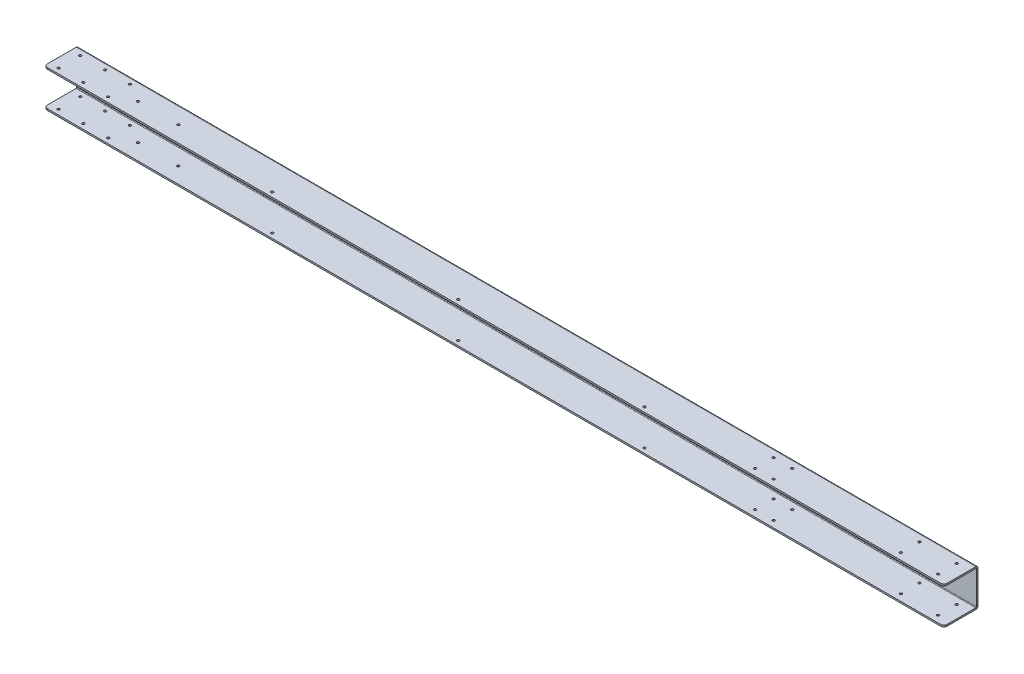
SolidWorks part; units mm, degrees
note: The reader was unsure of these and kept them because the rebuilt part matched: flange length of "Edge-Flange1".
material "5052-H32"
ref_plane "Front Plane" through (0, 0, 0) normal (0, 0, 1) x (1, 0, 0)
ref_plane "Top Plane" through (0, 0, 0) normal (0, 1, 0) x (1, 0, 0)
ref_plane "Right Plane" through (0, 0, 0) normal (1, 0, 0) x (0, 0, -1)
sketch "Sketch2" plane through (0, 0, 0) normal (0, 0, 1) x (1, 0, 0)
  line L1 (-920.75, 34.8361) -> (920.75, 34.8361)
  line L2 (-920.75, 34.8361) -> (-920.75, -34.8361)
  line L3 (-920.75, -34.8361) -> (920.75, -34.8361)
  line L4 (920.75, 34.8361) -> (920.75, -34.8361)
  line L5 (-920.75, 34.8361) -> (920.75, -34.8361) construction
  line L6 (-920.75, -34.8361) -> (920.75, 34.8361) construction
  point P0 (0, 0)
  dimension "D1" = 1841.5
  dimension "D2" = 69.6722
base flange "Base-Flange1" sketch "Sketch2" thickness 3.2639 reverse thickness direction no parameters "D1"=1.27
edge flange "Edge-Flange1" sketch "Sketch11" flange profiles "Sketch11", "Sketch12" flange angle 90 flange length 69.85 flange position material outside bend radius 1.27 thickness 3.2639 relief rectangular parameters "D6"=10, "D8"=0.254
sketch "Sketch11" plane through (0, 34.8361, 0) normal (0, 1, 0) x (-1, 0, 0)
  line L0 (-920.75, 0) -> (920.75, 0) construction
  line L1 (-920.75, 0) -> (920.75, 0)
  line L2 (-920.75, 0) -> (-920.75, 66.5861)
  line L3 (-920.75, 66.5861) -> (920.75, 66.5861)
  line L4 (920.75, 66.5861) -> (920.75, 0)
sketch "Sketch12" plane through (0, -34.8361, 0) normal (0, -1, 0) x (1, 0, 0)
  line L0 (-920.75, 0) -> (920.75, 0) construction
  line L1 (-920.75, 0) -> (920.75, 0)
  line L2 (-920.75, 0) -> (-920.75, 66.5861)
  line L3 (-920.75, 66.5861) -> (920.75, 66.5861)
  line L4 (920.75, 66.5861) -> (920.75, 0)
bend "EdgeBend1" bend radius 1.27 bend angle 90 parameters "D5"=1
bend "EdgeBend2" bend radius 1.27 bend angle 90 parameters "D5"=2
edge flange "Edge-Flange2" [suppressed] sketch "Sketch17" flange profiles "Sketch17", "Sketch18" flange angle 90 flange position material inside bend radius 1.27 thickness 3.2639
sketch "Sketch17" plane through (0, 34.8361, 66.5861) normal (0, 0, -1) x (1, 0, 0)
  line L2 (-920.75, 0) -> (-920.75, 11.9761)
  line L3 (-920.75, 11.9761) -> (920.75, 11.9761)
  line L4 (920.75, 11.9761) -> (920.75, 0)
  line L5 (920.75, 0) -> (-920.75, 0) construction
  line L6 (920.75, 0) -> (-920.75, 0)
sketch "Sketch18" plane through (0, -34.8361, 66.5861) normal (0, 0, -1) x (-1, 0, 0)
  line L0 (920.75, 0) -> (-920.75, 0) construction
  line L1 (920.75, 0) -> (-920.75, 0)
  line L2 (920.75, 0) -> (920.75, 11.9761)
  line L3 (920.75, 11.9761) -> (-920.75, 11.9761)
  line L4 (-920.75, 11.9761) -> (-920.75, 0)
bend "EdgeBend3" bend radius 1.27 bend angle 90 parameters "D5"=3
bend "EdgeBend4" bend radius 1.27 bend angle 90 parameters "D5"=4, "D6"=10, "D7"=15.24
sketch "Sketch26" plane through (0, 38.1, 0) normal (0, 1, 0) x (1, 0, 0)
  line L0 (-920.75, -1.27) -> (-920.75, -66.5861) construction
  line L1 (-901.7, -11.7031) -> (-800.1, -11.7031)
  line L2 (-901.7, -11.7031) -> (-901.7, -56.1531)
  line L3 (-901.7, -56.1531) -> (-800.1, -56.1531)
  line L4 (-800.1, -11.7031) -> (-800.1, -56.1531)
  point P6 (-850.9, -56.1531)
  point P7 (-920.75, -33.9281)
  point P8 (-901.7, -33.9281)
  point P10 (-850.9, -11.7031)
  dimension "D1" = 19.05
  dimension "D2" = 44.45
  dimension "D3" = 50.8
hole_wizard "#10 (0.1935) Diameter Hole1" positions "Sketch20" profile "Sketch21" hole size "#10" standard "ANSI Inch" end condition through all
sketch "Sketch20" plane through (0, 38.1, 34.8361) normal (0, -1, 0) x (-1, 0, 0)
  point P21 (800.1, 23.133)
  point P23 (800.1, -21.317)
  point P25 (850.9, -21.317)
  point P27 (850.9, 23.133)
  point P29 (901.7, -21.317)
  point P31 (901.7, 23.133)
sketch "Sketch21" plane through (-800.1, 38.1, 11.703) normal (1, 0, 0) x (0, 0, 1)
  line L0 (0, 0) -> (0, 76.2)
  line L1 (0, 76.2) -> (2.4574, 76.2)
  line L2 (2.4574, 76.2) -> (2.4574, 0)
  line L5 (2.4574, 0) -> (0, 0)
  line L11 (0, -6.35) -> (0, 107.95) construction
  dimension "Thru Hole Dia." = 4.9149
  dimension "Thru Hole Depth" = 76.2
sketch "Sketch22" [suppressed] plane through (0, 0, 82.3722) normal (0, 0, 1) x (1, 0, 0)
  line L0 (-920.75, 38.1) -> (920.75, 38.1) construction
  line L1 (-920.75, 22.86) -> (-920.75, 33.5661) construction
  line L2 (920.75, -38.1) -> (-920.75, -38.1) construction
  point P0 (-844.55, 28.575)
  point P5 (-844.55, -28.575)
  dimension "D1" = 9.525
  dimension "D2" = 76.2
  dimension "D3" = 9.525
hole_wizard "#10 (0.1935) Diameter Hole2" [suppressed] positions "Sketch23" profile "Sketch24" hole size "#10" standard "ANSI Inch"
sketch "Sketch23" [suppressed] plane through (0, 0, 82.3722) normal (0, 0, 1) x (1, 0, 0)
  point P0 (-844.55, 28.575)
  point P3 (-844.55, -28.575)
sketch "Sketch24" plane through (-844.55, 28.575, 82.3722) normal (1, 0, 0) x (0, -1, 0)
  line L0 (0, 0) -> (0, 85.6361)
  line L1 (0, 85.6361) -> (2.4574, 85.6361)
  line L2 (2.4574, 85.6361) -> (2.4574, 0)
  line L5 (2.4574, 0) -> (0, 0)
  line L11 (0, -6.35) -> (0, 107.95) construction
  dimension "Thru Hole Dia." = 4.9149
  dimension "Thru Hole Depth" = 85.6361
pattern_linear "LPattern1" [suppressed] count 11 spacing 168.91
sketch "Sketch27" plane through (0, 38.1, 0) normal (0, 1, 0) x (1, 0, 0)
  line L0 (819.15, -14.8781) -> (819.15, -52.9781) construction
  line L3 (895.35, -33.9281) -> (920.75, -33.9281) construction
  line L4 (895.35, -14.8781) -> (895.35, -52.9781) construction
  line L6 (920.75, -66.5861) -> (920.75, -1.27) construction
  dimension "D1" = 38.1
  dimension "D2" = 25.4
  dimension "D4" = 76.2
hole_wizard "#10 (0.1935) Diameter Hole3" positions "Sketch28" profile "Sketch29" hole size "#10" standard "ANSI Inch" end condition through all
sketch "Sketch28" plane through (0, 38.1, 0) normal (0, 1, 0) x (1, 0, 0)
  point P0 (819.15, -14.8781)
  point P3 (819.15, -52.9781)
  point P6 (895.35, -14.8781)
  point P9 (895.35, -52.9781)
sketch "Sketch29" plane through (819.15, 38.1, 14.878) normal (1, 0, 0) x (0, 0, 1)
  line L0 (0, 0) -> (0, 76.2)
  line L1 (0, 76.2) -> (2.4574, 76.2)
  line L2 (2.4574, 76.2) -> (2.4574, 0)
  line L5 (2.4574, 0) -> (0, 0)
  line L11 (0, -6.35) -> (0, 107.95) construction
  dimension "Thru Hole Dia." = 4.9149
  dimension "Thru Hole Depth" = 76.2
sketch "Sketch31" plane through (0, 38.1, 0) normal (0, 1, 0) x (1, 0, 0)
  line L0 (920.75, -66.5861) -> (920.75, -1.27) construction
  line L1 (520.7, -14.8781) -> (558.8, -14.8781)
  line L2 (520.7, -14.8781) -> (520.7, -52.9781)
  line L3 (520.7, -52.9781) -> (558.8, -52.9781)
  line L4 (558.8, -14.8781) -> (558.8, -52.9781)
  point P4 (558.8, -33.9281)
  point P7 (920.75, -33.9281)
  point P8 (539.75, -14.8781)
  dimension "D1" = 38.1
  dimension "D2" = 38.1
  dimension "D3" = 381
hole_wizard "#10 (0.1935) Diameter Hole4" positions "Sketch32" profile "Sketch33" hole size "#10" standard "ANSI Inch" end condition through all
sketch "Sketch32" plane through (0, 38.1, 0) normal (0, 1, 0) x (1, 0, 0)
  point P0 (520.7, -14.8781)
  point P3 (558.8, -14.8781)
  point P6 (558.8, -52.9781)
  point P9 (520.7, -52.9781)
sketch "Sketch33" plane through (520.7, 38.1, 14.878) normal (1, 0, 0) x (0, 0, 1)
  line L0 (0, 0) -> (0, 76.2)
  line L1 (0, 76.2) -> (2.4574, 76.2)
  line L2 (2.4574, 76.2) -> (2.4574, 0)
  line L5 (2.4574, 0) -> (0, 0)
  line L11 (0, -6.35) -> (0, 107.95) construction
  dimension "Thru Hole Dia." = 4.9149
  dimension "Thru Hole Depth" = 76.2
sketch "Sketch35" [suppressed] plane through (0, 38.1, 0) normal (0, 1, 0) x (1, 0, 0)
  line L0 (49980.8586, -68.2181) -> (-49980.8586, -68.2181) construction
  line L1 (920.75, -66.5861) -> (-920.75, -66.5861) construction
  line L2 (-787.4, -9.4361) -> (-787.4, -53.8861) construction
  circle A0 centre (-800.1, -53.8861) radius 2.4574 construction
  point P2 (0, -68.2181)
  point P12 (-762, -31.6611)
  point P13 (-679.45, -31.6611)
  point P14 (-787.4, -31.6611)
  dimension "D2" = 12.7
  dimension "D1" = 1.632
  dimension "D3" = 25.4
  dimension "D4" = 82.55
hole_wizard "#10 (0.1935) Diameter Hole5" [suppressed] positions "Sketch36" profile "Sketch37" hole size "#10" standard "ANSI Inch"
sketch "Sketch36" [suppressed] plane through (0, 38.1, 0) normal (0, 1, 0) x (1, 0, 0)
  point P0 (-762, -39.5542)
  point P3 (-679.45, -39.5542)
sketch "Sketch37" [suppressed] plane through (-762, 38.1, 39.5541) normal (1, 0, 0) x (0, 0, 1)
  line L0 (0, 0) -> (0, 76.2)
  line L1 (0, 76.2) -> (2.4574, 76.2)
  line L2 (2.4574, 76.2) -> (2.4574, 0)
  line L5 (2.4574, 0) -> (0, 0)
  line L11 (0, -6.35) -> (0, 107.95) construction
  dimension "Thru Hole Dia." = 4.9149
  dimension "Thru Hole Depth" = 76.2
fillet "Fillet1" [suppressed] radius 6.35
sketch "Sketch41" plane through (0, 38.1, 0) normal (0, 1, 0) x (1, 0, 0)
  line L0 (-800.1, -56.1531) -> (-800.1, -11.7031) construction
  point P4 (-761.3205, -33.9281)
  point P5 (-678.7705, -33.9281)
  point P6 (-800.1, -33.9281)
  dimension "D1" = 38.7794
  dimension "D2" = 82.55
hole_wizard "#10 (0.2) Diameter Hole1" positions "Sketch42" profile "Sketch43" hole size "#10" standard "ANSI Inch" end condition through all
sketch "Sketch42" plane through (0, 38.1, 0) normal (0, 1, 0) x (1, 0, 0)
  point P0 (-761.3205, -33.9281)
  point P3 (-678.7705, -33.9281)
sketch "Sketch43" plane through (-761.3205, 38.1, 33.928) normal (1, 0, 0) x (0, 0, 1)
  line L0 (0, 0) -> (0, 76.2)
  line L1 (0, 76.2) -> (2.54, 76.2)
  line L2 (2.54, 76.2) -> (2.54, 0)
  line L5 (2.54, 0) -> (0, 0)
  line L11 (0, -6.35) -> (0, 107.95) construction
  dimension "Thru Hole Dia." = 5.08
  dimension "Thru Hole Depth" = 76.2
sketch "Sketch38" plane through (0, -38.1, 0) normal (0, -1, 0) x (1, 0, 0)
  line L0 (-920.75, 66.5861) -> (-920.75, 1.27) construction
  line L1 (920.75, 66.5861) -> (-920.75, 66.5861) construction
  point P0 (-463.55, 57.0611)
  dimension "D1" = 457.2
  dimension "D2" = 9.525
hole_wizard "#10 (0.1935) Diameter Hole6" positions "Sketch39" profile "Sketch40" hole size "#10" standard "ANSI Inch" end condition through all
sketch "Sketch39" plane through (0, -38.1, 0) normal (0, -1, 0) x (-1, 0, 0)
  point P0 (463.55, -57.0611)
sketch "Sketch40" plane through (-463.55, -38.1, 57.0611) normal (1, 0, 0) x (0, 0, -1)
  line L0 (0, 0) -> (0, 76.2)
  line L1 (0, 76.2) -> (2.4574, 76.2)
  line L2 (2.4574, 76.2) -> (2.4574, 0)
  line L5 (2.4574, 0) -> (0, 0)
  line L11 (0, -6.35) -> (0, 107.95) construction
  dimension "Thru Hole Dia." = 4.9149
  dimension "Thru Hole Depth" = 76.2
pattern_linear "LPattern2" count 3 spacing 381 along (1, 0, 0) of "#10 (0.1935) Diameter Hole6"
fillet "Fillet2" radius 6.35 4 edges at (920.75, -36.4681, 66.5861) (920.75, 36.4681, 66.5861) (-920.75, -36.4681, 66.5861) (-920.75, 36.4681, 66.5861)
sketch "Bend-Lines1" [suppressed] plane through (0, 0, 0) normal (0, 1, 0) x (1, 0, 0)
sketch "Bounding-Box1" [suppressed] plane through (0, 0, 0) normal (0, 1, 0) x (1, 0, 0)
sheet metal parameters "Sheet-Metal1" thickness 3.2639 parameters "D1"=1.27
flat pattern "Flat-Pattern1" [suppressed]
sketch "Bend-Lines2" plane through (0, 0, 0) normal (0, 1, 0) x (1, 0, 0)
sketch3d "Bounding-Box2" [suppressed]
  line L0 (908.05, -44.45, 0) -> (-908.05, -44.45, 0) construction
  line L1 (908.05, 44.45, 0) -> (-908.05, 44.45, 0) construction
  line L2 (908.05, -44.45, 0) -> (908.05, 44.45, 0) construction
  line L3 (-908.05, -44.45, 0) -> (-908.05, 44.45, 0) construction
sheet metal parameters "Sheet-Metal2" thickness 3.2639 parameters "D1"=1.27
flat pattern "Flat-Pattern1" [suppressed]
sketch "Bend-Lines2" plane through (0, 0, 0) normal (0, 0, 1) x (1, 0, 0)
  line L0 (-908.05, -42.1953) -> (908.05, -42.1953) construction
  line L1 (908.05, 42.1953) -> (-908.05, 42.1953) construction
  line L2 (-908.05, -42.1953) -> (908.05, -42.1953) construction
  line L3 (908.05, 42.1953) -> (-908.05, 42.1953) construction
sketch3d "Bounding-Box2" [suppressed]
  line L0 (-908.05, -103.4406, 0) -> (908.05, -103.4406, 0) construction
  line L1 (-908.05, 103.4406, 0) -> (908.05, 103.4406, 0) construction
  line L2 (-908.05, -103.4406, 0) -> (-908.05, 103.4406, 0) construction
  line L3 (908.05, -103.4406, 0) -> (908.05, 103.4406, 0) construction
bend of the flat pattern "Flatten-<EdgeBend1>1"
bend of the flat pattern "Flatten-<EdgeBend2>1"
sheet metal parameters "Sheet-Metal3" thickness 3.2639 parameters "D1"=1.27
flat pattern "Flat-Pattern1" [suppressed]
sketch "Bend-Lines2" plane through (0, 0, 0) normal (0, 0, 1) x (1, 0, 0)
  line L0 (-920.75, -35.8453) -> (920.75, -35.8453) construction
  line L1 (920.75, 35.8453) -> (-920.75, 35.8453) construction
  line L2 (-920.75, -35.8453) -> (920.75, -35.8453) construction
  line L3 (920.75, 35.8453) -> (-920.75, 35.8453) construction
  line L4 (-920.75, -116.972) -> (920.75, -116.972) construction
  line L5 (920.75, 116.972) -> (-920.75, 116.972) construction
  line L6 (-920.75, -116.972) -> (920.75, -116.972) construction
  line L7 (920.75, 116.972) -> (-920.75, 116.972) construction
sketch3d "Bounding-Box2" [suppressed]
  line L0 (-920.75, -140.1172, 0) -> (920.75, -140.1172, 0) construction
  line L1 (-920.75, 140.1172, 0) -> (920.75, 140.1172, 0) construction
  line L2 (-920.75, -140.1172, 0) -> (-920.75, 140.1172, 0) construction
  line L3 (920.75, -140.1172, 0) -> (920.75, 140.1172, 0) construction
bend of the flat pattern "Flatten-<EdgeBend3>1"
bend of the flat pattern "Flatten-<EdgeBend4>1"
sketch "Sketch22-4" [suppressed] plane through (0, 152.8172, -3.2639) normal (0, 0, -1) x (1, 0, 0)
  line L0 (-920.75, 38.1) -> (920.75, 38.1)
  line L1 (-920.75, 12.7) -> (-920.75, 292.9345)
  line L2 (920.75, -38.1) -> (-920.75, -38.1)
  point P0 (-768.35, 22.225)
  point P5 (-768.35, -22.225)
  dimension "D1" = 15.875
  dimension "D2" = 152.4
  dimension "D3" = 15.875
bend of the flat pattern "Flatten-<EdgeBend1>1"
bend of the flat pattern "Flatten-<EdgeBend2>1"
sheet metal parameters "Sheet-Metal4" thickness 3.2639 parameters "D1"=1.27
flat pattern "Flat-Pattern1" [suppressed]
sketch "Bend-Lines2" plane through (0, 0, 0) normal (0, 0, 1) x (1, 0, 0)
  line L0 (-920.75, -35.8453) -> (920.75, -35.8453) construction
  line L1 (920.75, 35.8453) -> (-920.75, 35.8453) construction
  line L2 (-920.75, -35.8453) -> (920.75, -35.8453) construction
  line L3 (920.75, 35.8453) -> (-920.75, 35.8453) construction
  line L4 (-920.75, -116.972) -> (920.75, -116.972) construction
  line L5 (920.75, 116.972) -> (-920.75, 116.972) construction
  line L6 (-920.75, -116.972) -> (920.75, -116.972) construction
  line L7 (920.75, 116.972) -> (-920.75, 116.972) construction
sketch3d "Bounding-Box2" [suppressed]
  line L0 (-920.75, -140.1172, 0) -> (920.75, -140.1172, 0) construction
  line L1 (-920.75, 140.1172, 0) -> (920.75, 140.1172, 0) construction
  line L2 (-920.75, -140.1172, 0) -> (-920.75, 140.1172, 0) construction
  line L3 (920.75, -140.1172, 0) -> (920.75, 140.1172, 0) construction
sketch "Sketch22-3" [suppressed] plane through (0, 152.8172, -3.2639) normal (0, 0, -1) x (1, 0, 0)
  line L0 (-920.75, 38.1) -> (920.75, 38.1)
  line L1 (-920.75, 12.7) -> (-920.75, 292.9345)
  line L2 (920.75, -38.1) -> (-920.75, -38.1)
  point P0 (-768.35, 22.225)
  point P5 (-768.35, -22.225)
  dimension "D1" = 15.875
  dimension "D2" = 152.4
  dimension "D3" = 15.875
sketch "Sketch26-1" [suppressed] plane through (0, 36.8545, -3.2639) normal (0, 0, -1) x (1, 0, 0)
  line L0 (-920.75, 176.9717) -> (-920.75, -103.2628)
  line L1 (-901.7, -14.1542) -> (-800.1, -14.1542)
  line L2 (-901.7, -14.1542) -> (-901.7, -64.9542)
  line L3 (-901.7, -64.9542) -> (-800.1, -64.9542)
  line L4 (-800.1, -14.1542) -> (-800.1, -64.9542)
  point P6 (-850.9, -64.9542)
  point P10 (-850.9, -14.1542)
  dimension "D1" = 19.05
  dimension "D2" = 50.8
  dimension "D3" = 50.8
bend of the flat pattern "Flatten-<EdgeBend1>1"
bend of the flat pattern "Flatten-<EdgeBend2>1"
sheet metal parameters "Sheet-Metal6" thickness 3.2639 parameters "D1"=1.27
flat pattern "Flat-Pattern1" [suppressed]
sketch "Bend-Lines2" plane through (0, 0, 0) normal (0, 0, 1) x (1, 0, 0)
  line L0 (-923.925, -42.1953) -> (923.925, -42.1953) construction
  line L1 (923.925, 42.1953) -> (-923.925, 42.1953) construction
  line L2 (-923.925, -42.1953) -> (923.925, -42.1953) construction
  line L3 (923.925, 42.1953) -> (-923.925, 42.1953) construction
  line L4 (-923.925, -110.622) -> (923.925, -110.622) construction
  line L5 (923.925, 110.622) -> (-923.925, 110.622) construction
  line L6 (-923.925, -110.622) -> (923.925, -110.622) construction
  line L7 (923.925, 110.622) -> (-923.925, 110.622) construction
sketch3d "Bounding-Box2" [suppressed]
  line L0 (-923.925, -133.7672, 0) -> (923.925, -133.7672, 0) construction
  line L1 (-923.925, 133.7672, 0) -> (923.925, 133.7672, 0) construction
  line L2 (-923.925, -133.7672, 0) -> (-923.925, 133.7672, 0) construction
  line L3 (923.925, -133.7672, 0) -> (923.925, 133.7672, 0) construction
bend of the flat pattern "Flatten-<EdgeBend3>1"
bend of the flat pattern "Flatten-<EdgeBend4>1"
sketch "Sketch22-1" [suppressed] plane through (0, 152.8172, -3.2639) normal (0, 0, -1) x (1, 0, 0)
  line L0 (-923.925, 44.45) -> (923.925, 44.45)
  line L1 (-923.925, 19.05) -> (-923.925, 286.5845)
  line L2 (923.925, -44.45) -> (-923.925, -44.45)
  point P0 (-796.925, 28.575)
  point P5 (-796.925, -28.575)
  dimension "D1" = 15.875
  dimension "D2" = 127
  dimension "D3" = 15.875
sheet metal parameters "Sheet-Metal7" thickness 3.2639 parameters "D1"=1.27
flat pattern "Flat-Pattern1" [suppressed]
sketch "Bend-Lines2" plane through (0, 0, 0) normal (0, 0, 1) x (1, 0, 0)
  line L0 (-920.75, -35.8453) -> (920.75, -35.8453) construction
  line L1 (920.75, 35.8453) -> (-920.75, 35.8453) construction
  line L2 (-920.75, -35.8453) -> (920.75, -35.8453) construction
  line L3 (920.75, 35.8453) -> (-920.75, 35.8453) construction
  line L4 (-920.75, -116.972) -> (920.75, -116.972) construction
  line L5 (920.75, 116.972) -> (-920.75, 116.972) construction
  line L6 (-920.75, -116.972) -> (920.75, -116.972) construction
  line L7 (920.75, 116.972) -> (-920.75, 116.972) construction
sketch3d "Bounding-Box2" [suppressed]
  line L0 (-920.75, -140.1172, 0) -> (920.75, -140.1172, 0) construction
  line L1 (-920.75, 140.1172, 0) -> (920.75, 140.1172, 0) construction
  line L2 (-920.75, -140.1172, 0) -> (-920.75, 140.1172, 0) construction
  line L3 (920.75, -140.1172, 0) -> (920.75, 140.1172, 0) construction
bend of the flat pattern "Flatten-<EdgeBend3>1"
bend of the flat pattern "Flatten-<EdgeBend4>1"
sketch "Sketch22-1" [suppressed] plane through (0, 152.8172, -3.2639) normal (0, 0, -1) x (1, 0, 0)
  line L0 (-920.75, 38.1) -> (920.75, 38.1)
  line L1 (-920.75, 12.7) -> (-920.75, 292.9345)
  line L2 (920.75, -38.1) -> (-920.75, -38.1)
  point P0 (-844.55, 22.225)
  point P5 (-844.55, -22.225)
  dimension "D1" = 15.875
  dimension "D2" = 76.2
  dimension "D3" = 15.875
sketch "Sketch26-2" [suppressed] plane through (0, 36.8545, -3.2639) normal (0, 0, -1) x (1, 0, 0)
  line L0 (-920.75, 176.9717) -> (-920.75, -103.2628)
  line L1 (-901.7, -14.1542) -> (-800.1, -14.1542)
  line L2 (-901.7, -14.1542) -> (-901.7, -64.9542)
  line L3 (-901.7, -64.9542) -> (-800.1, -64.9542)
  line L4 (-800.1, -14.1542) -> (-800.1, -64.9542)
  point P6 (-850.9, -64.9542)
  point P10 (-850.9, -14.1542)
  dimension "D1" = 19.05
  dimension "D2" = 50.8
  dimension "D3" = 50.8
sheet metal parameters "Sheet-Metal8" thickness 3.2639 parameters "D1"=1.27
flat pattern "Flat-Pattern1" [suppressed]
sketch "Bend-Lines2" plane through (0, 0, 0) normal (0, 0, 1) x (1, 0, 0)
  line L0 (-920.75, -35.8453) -> (920.75, -35.8453) construction
  line L1 (920.75, 35.8453) -> (-920.75, 35.8453) construction
  line L2 (-920.75, -35.8453) -> (920.75, -35.8453) construction
  line L3 (920.75, 35.8453) -> (-920.75, 35.8453) construction
  line L4 (-920.75, -116.972) -> (920.75, -116.972) construction
  line L5 (920.75, 116.972) -> (-920.75, 116.972) construction
  line L6 (-920.75, -116.972) -> (920.75, -116.972) construction
  line L7 (920.75, 116.972) -> (-920.75, 116.972) construction
sketch3d "Bounding-Box2" [suppressed]
  line L0 (-920.75, -140.1172, 0) -> (920.75, -140.1172, 0) construction
  line L1 (-920.75, 140.1172, 0) -> (920.75, 140.1172, 0) construction
  line L2 (-920.75, -140.1172, 0) -> (-920.75, 140.1172, 0) construction
  line L3 (920.75, -140.1172, 0) -> (920.75, 140.1172, 0) construction
sketch "Sketch22-1" [suppressed] plane through (0, 152.8172, -3.2639) normal (0, 0, -1) x (1, 0, 0)
  line L0 (-920.75, 38.1) -> (920.75, 38.1)
  line L1 (-920.75, 12.7) -> (-920.75, 292.9345)
  line L2 (920.75, -38.1) -> (-920.75, -38.1)
  point P0 (-844.55, 22.225)
  point P5 (-844.55, -22.225)
  dimension "D1" = 15.875
  dimension "D2" = 76.2
  dimension "D3" = 15.875
sketch "Sketch26-2" [suppressed] plane through (0, 36.8545, -3.2639) normal (0, 0, -1) x (1, 0, 0)
  line L0 (-920.75, 176.9717) -> (-920.75, -103.2628)
  line L1 (-901.7, -14.1542) -> (-800.1, -14.1542)
  line L2 (-901.7, -14.1542) -> (-901.7, -64.9542)
  line L3 (-901.7, -64.9542) -> (-800.1, -64.9542)
  line L4 (-800.1, -14.1542) -> (-800.1, -64.9542)
  point P6 (-850.9, -64.9542)
  point P10 (-850.9, -14.1542)
  dimension "D1" = 19.05
  dimension "D2" = 50.8
  dimension "D3" = 50.8
sketch "Sketch27-1" [suppressed] plane through (0, 36.8545, -3.2639) normal (0, 0, -1) x (1, 0, 0)
  line L0 (806.5132, -15.7861) -> (806.5132, -66.5861) construction
  line L1 (671.8955, -85.6361) -> (50671.8955, -85.6361) construction
  line L2 (-920.75, 3.2639) -> (920.75, 3.2639)
  line L3 (920.75, 3.2639) -> (920.75, -85.6361) construction
  line L4 (882.7132, -15.7861) -> (882.7132, -66.5861) construction
  dimension "D1" = 50.8
  dimension "D2" = 88.9
  dimension "D3" = 114.2368
  dimension "D4" = 76.2
bend of the flat pattern "Flatten-<EdgeBend1>1"
bend of the flat pattern "Flatten-<EdgeBend2>1"
sheet metal parameters "Sheet-Metal9" thickness 3.2639 parameters "D1"=1.27
flat pattern "Flat-Pattern1" [suppressed]
sketch "Bend-Lines2" plane through (0, 0, 0) normal (0, 0, 1) x (1, 0, 0)
  line L0 (-920.75, -35.9342) -> (920.75, -35.9342) construction
  line L1 (920.75, 35.9342) -> (-920.75, 35.9342) construction
  line L2 (-920.75, -35.9342) -> (920.75, -35.9342) construction
  line L3 (920.75, 35.9342) -> (-920.75, 35.9342) construction
sketch3d "Bounding-Box2" [suppressed]
  line L0 (-920.75, 103.5297, 0) -> (920.75, 103.5295, 0) construction
  line L1 (-920.75, -103.5293, 0) -> (920.75, -103.5295, 0) construction
  line L2 (-920.75, 103.5297, 0) -> (-920.75, -103.5293, 0) construction
  line L3 (920.75, 103.5295, 0) -> (920.75, -103.5295, 0) construction
sketch "Sketch22-1" [suppressed] plane through (0, 152.8172, -3.2639) normal (0, 0, -1) x (1, 0, 0)
  line L0 (-920.75, 38.1) -> (920.75, 38.1)
  line L1 (-920.75, 12.7) -> (-920.75, 292.9345)
  line L2 (920.75, -38.1) -> (-920.75, -38.1)
  point P0 (-844.55, 22.225)
  point P5 (-844.55, -22.225)
  dimension "D1" = 15.875
  dimension "D2" = 76.2
  dimension "D3" = 15.875
sketch "Sketch26-2" plane through (0, 36.9434, -3.2639) normal (0, 0, -1) x (1, 0, 0)
  line L0 (-920.75, 134.1228) -> (-920.75, -60.2361) construction
  line L1 (-901.7, -11.7031) -> (-800.1, -11.7031)
  line L2 (-901.7, -11.7031) -> (-901.7, -56.1531)
  line L3 (-901.7, -56.1531) -> (-800.1, -56.1531)
  line L4 (-800.1, -11.7031) -> (-800.1, -56.1531)
  point P6 (-850.9, -56.1531)
  point P10 (-850.9, -11.7031)
  dimension "D1" = 19.05
  dimension "D2" = 44.45
  dimension "D3" = 50.8
sketch "Sketch27-1" [suppressed] plane through (0, 36.9434, 0) normal (0, 0, -1) x (1, 0, 0)
  line L0 (806.5132, -22.1361) -> (806.5132, -60.2361) construction
  line L1 (671.8955, -85.6361) -> (50671.8955, -85.6361) construction
  line L2 (-920.75, 3.2639) -> (920.75, 3.2639) construction
  line L3 (920.75, 3.2639) -> (920.75, -85.6361) construction
  line L4 (882.7132, -22.1361) -> (882.7132, -60.2361) construction
  dimension "D1" = 38.1
  dimension "D2" = 88.9
  dimension "D3" = 114.2368
  dimension "D4" = 76.2
sketch "Sketch31-1" plane through (0, 36.9434, -3.2639) normal (0, 0, -1) x (1, 0, 0)
  line L1 (520.7, -14.8781) -> (558.8, -14.8781)
  line L2 (520.7, -14.8781) -> (520.7, -52.9781)
  line L3 (520.7, -52.9781) -> (558.8, -52.9781)
  line L4 (558.8, -14.8781) -> (558.8, -52.9781)
  dimension "D1" = 38.1
  dimension "D2" = 38.1
sketch "Sketch35-2" [suppressed] plane through (0, 36.9434, -3.175) normal (0, 0, -1) x (1, 0, 0)
  line L0 (49980.8586, -84.0042) -> (-49980.8586, -84.0042) construction
  line L1 (920.75, -82.3722) -> (-920.75, -82.3722) construction
  line L2 (-787.4, -14.1542) -> (-787.4, -64.9542) construction
  circle A0 centre (-800.1, -56.1531) radius 2.4574 construction
  point P12 (-762, -39.5542)
  point P13 (-679.45, -39.5542)
  dimension "D2" = 12.7
  dimension "D1" = 1.632
  dimension "D3" = 25.4
  dimension "D4" = 82.55
bend of the flat pattern "Flatten-<EdgeBend1>1"
bend of the flat pattern "Flatten-<EdgeBend2>1"
sheet metal parameters "Sheet-Metal10" thickness 3.2639 parameters "D1"=1.27
flat pattern "Flat-Pattern1" [suppressed]
sketch "Bend-Lines2" plane through (0, 0, 0) normal (0, 0, 1) x (1, 0, 0)
  line L0 (-920.75, -35.8453) -> (920.75, -35.8453) construction
  line L1 (920.75, 35.8453) -> (-920.75, 35.8453) construction
  line L2 (-920.75, -35.8453) -> (920.75, -35.8453) construction
  line L3 (920.75, 35.8453) -> (-920.75, 35.8453) construction
  line L4 (-920.75, -116.972) -> (920.75, -116.972) construction
  line L5 (920.75, 116.972) -> (-920.75, 116.972) construction
  line L6 (-920.75, -116.972) -> (920.75, -116.972) construction
  line L7 (920.75, 116.972) -> (-920.75, 116.972) construction
sketch3d "Bounding-Box2" [suppressed]
  line L0 (-920.75, 129.9574, 0) -> (920.75, 129.9572, 0) construction
  line L1 (-920.75, -129.9571, 0) -> (920.75, -129.9572, 0) construction
  line L2 (-920.75, 129.9574, 0) -> (-920.75, -129.9571, 0) construction
  line L3 (920.75, 129.9572, 0) -> (920.75, -129.9572, 0) construction
bend of the flat pattern "Flatten-<EdgeBend3>1"
bend of the flat pattern "Flatten-<EdgeBend4>1"
sketch "Sketch22-1" [suppressed] plane through (0, 152.8172, -3.2639) normal (0, 0, -1) x (1, 0, 0)
  line L0 (-920.75, 38.1) -> (920.75, 38.1) construction
  line L1 (-920.75, 29.21) -> (-920.75, 276.4245) construction
  line L2 (920.75, -38.1) -> (-920.75, -38.1) construction
  point P0 (-844.55, 28.575)
  point P5 (-844.55, -28.575)
  dimension "D1" = 9.525
  dimension "D2" = 76.2
  dimension "D3" = 9.525
sketch "Sketch26-2" [suppressed] plane through (0, 36.8545, -3.2639) normal (0, 0, -1) x (1, 0, 0)
  line L0 (-920.75, 160.4617) -> (-920.75, -86.7528) construction
  line L1 (-901.7, -14.1542) -> (-800.1, -14.1542)
  line L2 (-901.7, -14.1542) -> (-901.7, -64.9542)
  line L3 (-901.7, -64.9542) -> (-800.1, -64.9542)
  line L4 (-800.1, -14.1542) -> (-800.1, -64.9542)
  point P6 (-850.9, -64.9542)
  point P10 (-850.9, -14.1542)
  dimension "D1" = 19.05
  dimension "D2" = 50.8
  dimension "D3" = 50.8
sketch "Sketch27-1" [suppressed] plane through (0, 36.8545, -3.2639) normal (0, 0, -1) x (1, 0, 0)
  line L0 (806.5132, -15.7861) -> (806.5132, -66.5861) construction
  line L1 (671.8955, -85.6361) -> (50671.8955, -85.6361) construction
  line L2 (-920.75, 3.2639) -> (920.75, 3.2639) construction
  line L3 (920.75, 3.2639) -> (920.75, -85.6361) construction
  line L4 (882.7132, -15.7861) -> (882.7132, -66.5861) construction
  dimension "D1" = 50.8
  dimension "D2" = 88.9
  dimension "D3" = 114.2368
  dimension "D4" = 76.2
sketch "Sketch31-1" [suppressed] plane through (0, 36.8545, -3.2639) normal (0, 0, -1) x (1, 0, 0)
  line L1 (520.7, -20.5042) -> (558.8, -20.5042)
  line L2 (520.7, -20.5042) -> (520.7, -58.6042)
  line L3 (520.7, -58.6042) -> (558.8, -58.6042)
  line L4 (558.8, -20.5042) -> (558.8, -58.6042)
  dimension "D1" = 38.1
  dimension "D2" = 38.1
sketch "Sketch35-1" [suppressed] plane through (0, 36.8545, -3.2639) normal (0, 0, -1) x (1, 0, 0)
  line L0 (49980.8586, -84.0042) -> (-49980.8586, -84.0042) construction
  line L1 (920.75, -82.3722) -> (-920.75, -82.3722) construction
  line L2 (-787.4, -14.1542) -> (-787.4, -64.9542) construction
  circle A0 centre (-800.1, -64.9542) radius 2.4574 construction
  point P12 (-762, -39.5542)
  point P13 (-679.45, -39.5542)
  dimension "D2" = 12.7
  dimension "D1" = 1.632
  dimension "D3" = 25.4
  dimension "D4" = 82.55
sheet metal parameters "Sheet-Metal25" thickness 3.2639 parameters "D1"=1.27
flat pattern "Flat-Pattern1" [suppressed]
sketch "Bend-Lines2" plane through (0, 0, 0) normal (0, 0, 1) x (1, 0, 0)
  line L0 (-920.75, -35.9342) -> (920.75, -35.9342) construction
  line L1 (920.75, 35.9342) -> (-920.75, 35.9342) construction
  line L2 (-920.75, -35.9342) -> (920.75, -35.9342) construction
  line L3 (920.75, 35.9342) -> (-920.75, 35.9342) construction
sketch3d "Bounding-Box2" [suppressed]
  line L0 (-920.75, 103.5297, 0) -> (920.75, 103.5295, 0) construction
  line L1 (-920.75, -103.5293, 0) -> (920.75, -103.5295, 0) construction
  line L2 (-920.75, 103.5297, 0) -> (-920.75, -103.5293, 0) construction
  line L3 (920.75, 103.5295, 0) -> (920.75, -103.5295, 0) construction
sketch "Sketch22-1" [suppressed] plane through (0, 152.8172, -3.2639) normal (0, 0, -1) x (1, 0, 0)
  line L0 (-920.75, 38.1) -> (920.75, 38.1)
  line L1 (-920.75, 12.7) -> (-920.75, 292.9345)
  line L2 (920.75, -38.1) -> (-920.75, -38.1)
  point P0 (-844.55, 22.225)
  point P5 (-844.55, -22.225)
  dimension "D1" = 15.875
  dimension "D2" = 76.2
  dimension "D3" = 15.875
sketch "Sketch26-2" plane through (0, 36.9434, -3.2639) normal (0, 0, -1) x (1, 0, 0)
  line L0 (-920.75, 134.1228) -> (-920.75, -60.2361) construction
  line L1 (-901.7, -11.7031) -> (-800.1, -11.7031)
  line L2 (-901.7, -11.7031) -> (-901.7, -56.1531)
  line L3 (-901.7, -56.1531) -> (-800.1, -56.1531)
  line L4 (-800.1, -11.7031) -> (-800.1, -56.1531)
  point P6 (-850.9, -56.1531)
  point P10 (-850.9, -11.7031)
  dimension "D1" = 19.05
  dimension "D2" = 44.45
  dimension "D3" = 50.8
sketch "Sketch27-1" [suppressed] plane through (0, 36.9434, 0) normal (0, 0, -1) x (1, 0, 0)
  line L0 (806.5132, -22.1361) -> (806.5132, -60.2361) construction
  line L1 (671.8955, -85.6361) -> (50671.8955, -85.6361) construction
  line L2 (-920.75, 3.2639) -> (920.75, 3.2639) construction
  line L3 (920.75, 3.2639) -> (920.75, -85.6361) construction
  line L4 (882.7132, -22.1361) -> (882.7132, -60.2361) construction
  dimension "D1" = 38.1
  dimension "D2" = 88.9
  dimension "D3" = 114.2368
  dimension "D4" = 76.2
sketch "Sketch31-1" plane through (0, 36.9434, -3.2639) normal (0, 0, -1) x (1, 0, 0)
  line L1 (520.7, -14.8781) -> (558.8, -14.8781)
  line L2 (520.7, -14.8781) -> (520.7, -52.9781)
  line L3 (520.7, -52.9781) -> (558.8, -52.9781)
  line L4 (558.8, -14.8781) -> (558.8, -52.9781)
  dimension "D1" = 38.1
  dimension "D2" = 38.1
sketch "Sketch35-2" [suppressed] plane through (0, 36.9434, -3.175) normal (0, 0, -1) x (1, 0, 0)
  line L0 (49980.8586, -84.0042) -> (-49980.8586, -84.0042) construction
  line L1 (920.75, -82.3722) -> (-920.75, -82.3722) construction
  line L2 (-787.4, -14.1542) -> (-787.4, -64.9542) construction
  circle A0 centre (-800.1, -56.1531) radius 2.4574 construction
  point P12 (-762, -39.5542)
  point P13 (-679.45, -39.5542)
  dimension "D2" = 12.7
  dimension "D1" = 1.632
  dimension "D3" = 25.4
  dimension "D4" = 82.55
sketch "Sketch38-1" [suppressed] plane through (0, -36.9434, -3.2639) normal (0, 0, -1) x (1, 0, 0)
  line L0 (-920.75, 60.2361) -> (-920.75, -134.1228) construction
  line L1 (914.4, 66.5861) -> (-914.4, 66.5861) construction
  point P0 (-666.75, 57.0611)
  dimension "D1" = 254
  dimension "D2" = 9.525
bend of the flat pattern "Flatten-<EdgeBend1>1"
bend of the flat pattern "Flatten-<EdgeBend2>1"
sheet metal parameters "Sheet-Metal26" thickness 3.2639 parameters "D1"=1.27
flat pattern "Flat-Pattern1" [suppressed]
sketch "Bend-Lines2" plane through (0, 0, 0) normal (0, 0, 1) x (1, 0, 0)
  line L0 (-920.75, -35.8453) -> (920.75, -35.8453) construction
  line L1 (920.75, 35.8453) -> (-920.75, 35.8453) construction
  line L2 (-920.75, -35.8453) -> (920.75, -35.8453) construction
  line L3 (920.75, 35.8453) -> (-920.75, 35.8453) construction
sketch3d "Bounding-Box2" [suppressed]
  line L0 (-920.75, 103.4408, 0) -> (920.75, 103.4406, 0) construction
  line L1 (-920.75, -103.4404, 0) -> (920.75, -103.4406, 0) construction
  line L2 (-920.75, 103.4408, 0) -> (-920.75, -103.4404, 0) construction
  line L3 (920.75, 103.4406, 0) -> (920.75, -103.4406, 0) construction
bend of the flat pattern "Flatten-<EdgeBend1>1"
bend of the flat pattern "Flatten-<EdgeBend2>1"
sketch "Sketch22-1" [suppressed] plane through (0, 137.0311, -19.05) normal (0, 0, -1) x (1, 0, 0)
  line L0 (-920.75, 38.1) -> (920.75, 38.1) construction
  line L1 (-920.75, 22.86) -> (-920.75, 251.2023) construction
  line L2 (920.75, -38.1) -> (-920.75, -38.1) construction
  point P0 (-844.55, 28.575)
  point P5 (-844.55, -28.575)
  dimension "D1" = 9.525
  dimension "D2" = 76.2
  dimension "D3" = 9.525
sketch "Sketch26-2" plane through (0, 36.8545, -3.2639) normal (0, 0, -1) x (1, 0, 0)
  line L0 (-920.75, 133.945) -> (-920.75, -60.2361) construction
  line L1 (-901.7, -11.7031) -> (-800.1, -11.7031)
  line L2 (-901.7, -11.7031) -> (-901.7, -56.1531)
  line L3 (-901.7, -56.1531) -> (-800.1, -56.1531)
  line L4 (-800.1, -11.7031) -> (-800.1, -56.1531)
  point P6 (-850.9, -56.1531)
  point P10 (-850.9, -11.7031)
  dimension "D1" = 19.05
  dimension "D2" = 44.45
  dimension "D3" = 50.8
sketch "Sketch27-1" plane through (0, 36.8545, -3.2639) normal (0, 0, -1) x (1, 0, 0)
  line L0 (819.15, -14.8781) -> (819.15, -52.9781) construction
  line L3 (895.35, -33.9281) -> (920.75, -33.9281) construction
  line L4 (895.35, -14.8781) -> (895.35, -52.9781) construction
  dimension "D1" = 38.1
  dimension "D2" = 25.4
  dimension "D4" = 76.2
sketch "Sketch31-1" plane through (0, 36.8545, -3.2639) normal (0, 0, -1) x (1, 0, 0)
  line L1 (520.7, -14.8781) -> (558.8, -14.8781)
  line L2 (520.7, -14.8781) -> (520.7, -52.9781)
  line L3 (520.7, -52.9781) -> (558.8, -52.9781)
  line L4 (558.8, -14.8781) -> (558.8, -52.9781)
  dimension "D1" = 38.1
  dimension "D2" = 38.1
sketch "Sketch35-2" [suppressed] plane through (0, 36.8545, -3.2639) normal (0, 0, -1) x (1, 0, 0)
  line L0 (49980.8586, -68.2181) -> (-49980.8586, -68.2181) construction
  line L1 (920.75, -66.5861) -> (-920.75, -66.5861) construction
  line L2 (-787.4, -9.4361) -> (-787.4, -53.8861) construction
  circle A0 centre (-800.1, -56.1531) radius 2.4574 construction
  point P12 (-762, -31.6611)
  point P13 (-679.45, -31.6611)
  dimension "D2" = 12.7
  dimension "D1" = 1.632
  dimension "D3" = 25.4
  dimension "D4" = 82.55
sketch "Sketch38-1" [suppressed] plane through (0, -36.8545, -3.2639) normal (0, 0, -1) x (1, 0, 0)
  line L0 (-920.75, 60.2361) -> (-920.75, -133.945) construction
  line L1 (914.4, 66.5861) -> (-914.4, 66.5861) construction
  point P0 (-463.55, 57.0611)
  dimension "D1" = 457.2
  dimension "D2" = 9.525
sketch "Sketch41-2" [suppressed] plane through (0, 36.8545, -3.2639) normal (0, 0, -1) x (1, 0, 0)
  line L0 (-800.1, -56.1531) -> (-800.1, -11.7031) construction
  point P4 (-761.3205, -33.9281)
  point P5 (-678.7705, -33.9281)
  dimension "D1" = 38.7794
  dimension "D2" = 82.55
sheet metal parameters "Sheet-Metal27" thickness 3.2639 parameters "D1"=1.27
flat pattern "Flat-Pattern1" [suppressed]
sketch "Bend-Lines2" plane through (0, 0, 0) normal (0, 0, 1) x (1, 0, 0)
  line L0 (-920.75, -35.8453) -> (920.75, -35.8453) construction
  line L1 (920.75, 35.8453) -> (-920.75, 35.8453) construction
  line L2 (-920.75, -35.8453) -> (920.75, -35.8453) construction
  line L3 (920.75, 35.8453) -> (-920.75, 35.8453) construction
sketch3d "Bounding-Box2" [suppressed]
  line L0 (-920.75, 103.4408, 0) -> (920.75, 103.4406, 0) construction
  line L1 (-920.75, -103.4404, 0) -> (920.75, -103.4406, 0) construction
  line L2 (-920.75, 103.4408, 0) -> (-920.75, -103.4404, 0) construction
  line L3 (920.75, 103.4406, 0) -> (920.75, -103.4406, 0) construction
bend of the flat pattern "Flatten-<EdgeBend1>1"
bend of the flat pattern "Flatten-<EdgeBend2>1"
sketch "Sketch22-1" [suppressed] plane through (0, 137.0311, -19.05) normal (0, 0, -1) x (1, 0, 0)
  line L0 (-920.75, 38.1) -> (920.75, 38.1)
  line L1 (-920.75, 22.86) -> (-920.75, 251.2023)
  line L2 (920.75, -38.1) -> (-920.75, -38.1)
  point P0 (-844.55, 28.575)
  point P5 (-844.55, -28.575)
  dimension "D1" = 9.525
  dimension "D2" = 76.2
  dimension "D3" = 9.525
sketch "Sketch26-2" plane through (0, 36.8545, -3.2639) normal (0, 0, -1) x (1, 0, 0)
  line L0 (-920.75, 133.945) -> (-920.75, -60.2361) construction
  line L1 (-901.7, -11.7031) -> (-800.1, -11.7031)
  line L2 (-901.7, -11.7031) -> (-901.7, -56.1531)
  line L3 (-901.7, -56.1531) -> (-800.1, -56.1531)
  line L4 (-800.1, -11.7031) -> (-800.1, -56.1531)
  point P6 (-850.9, -56.1531)
  point P10 (-850.9, -11.7031)
  dimension "D1" = 19.05
  dimension "D2" = 44.45
  dimension "D3" = 50.8
sketch "Sketch27-1" [suppressed] plane through (0, 36.8545, -0.0889) normal (0, 0, -1) x (1, 0, 0)
  line L0 (806.5132, -22.1361) -> (806.5132, -60.2361) construction
  line L1 (671.8955, -85.6361) -> (50671.8955, -85.6361) construction
  line L2 (-920.75, 3.2639) -> (920.75, 3.2639) construction
  line L3 (920.75, 3.2639) -> (920.75, -85.6361) construction
  line L4 (882.7132, -22.1361) -> (882.7132, -60.2361) construction
  dimension "D1" = 38.1
  dimension "D2" = 88.9
  dimension "D3" = 114.2368
  dimension "D4" = 76.2
sketch "Sketch31-1" plane through (0, 36.8545, -3.2639) normal (0, 0, -1) x (1, 0, 0)
  line L1 (520.7, -14.8781) -> (558.8, -14.8781)
  line L2 (520.7, -14.8781) -> (520.7, -52.9781)
  line L3 (520.7, -52.9781) -> (558.8, -52.9781)
  line L4 (558.8, -14.8781) -> (558.8, -52.9781)
  dimension "D1" = 38.1
  dimension "D2" = 38.1
sketch "Sketch35-2" [suppressed] plane through (0, 36.8545, -3.2639) normal (0, 0, -1) x (1, 0, 0)
  line L0 (49980.8586, -68.2181) -> (-49980.8586, -68.2181) construction
  line L1 (920.75, -66.5861) -> (-920.75, -66.5861) construction
  line L2 (-787.4, -9.4361) -> (-787.4, -53.8861) construction
  circle A0 centre (-800.1, -56.1531) radius 2.4574 construction
  point P12 (-762, -31.6611)
  point P13 (-679.45, -31.6611)
  dimension "D2" = 12.7
  dimension "D1" = 1.632
  dimension "D3" = 25.4
  dimension "D4" = 82.55
sketch "Sketch38-1" [suppressed] plane through (0, -36.8545, -3.2639) normal (0, 0, -1) x (1, 0, 0)
  line L0 (-920.75, 60.2361) -> (-920.75, -133.945) construction
  line L1 (914.4, 66.5861) -> (-914.4, 66.5861) construction
  point P0 (-666.75, 57.0611)
  dimension "D1" = 254
  dimension "D2" = 9.525
sketch "Sketch41-1" [suppressed] plane through (0, 36.8545, -3.2639) normal (0, 0, -1) x (1, 0, 0)
  line L0 (-800.1, -56.1531) -> (-800.1, -11.7031) construction
  point P4 (-761.3205, -33.9281)
  point P5 (-678.7705, -33.9281)
  dimension "D1" = 38.7794
  dimension "D2" = 82.55
